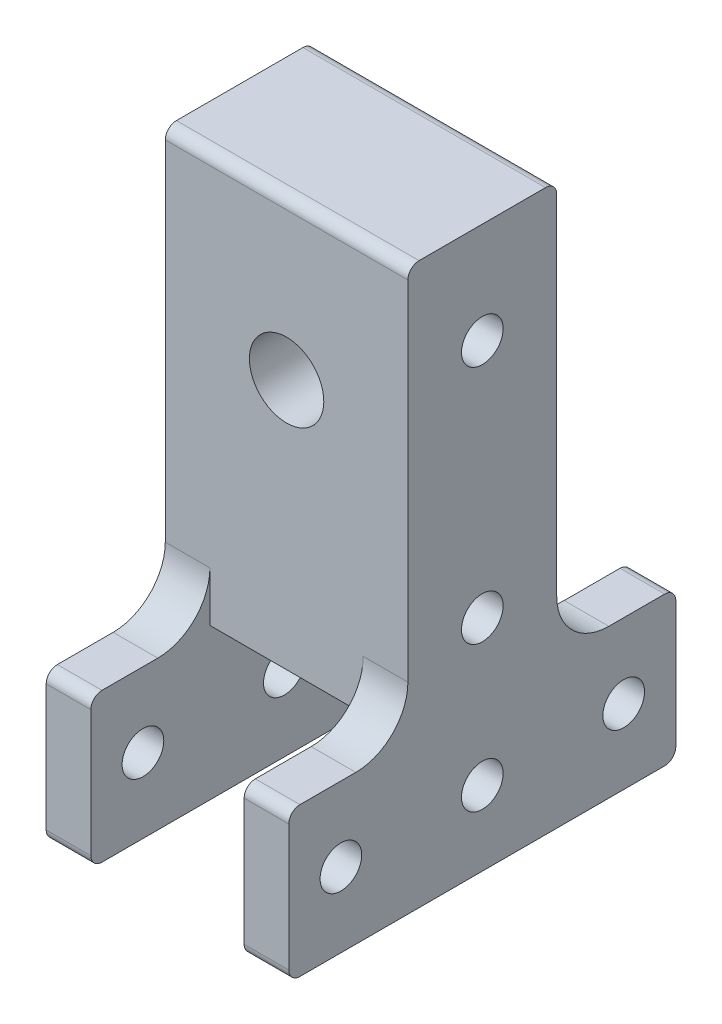
SolidWorks part; units mm, degrees
ref_plane "Front plane" through (0, 0, 0) normal (0, 0, 1) x (1, 0, 0)
ref_plane "Top plane" through (0, 0, 0) normal (0, 1, 0) x (1, 0, 0)
ref_plane "Right plane" through (0, 0, 0) normal (1, 0, 0) x (0, 0, -1)
ref_axis "Axis X" through (0, 0, 0) along (1, 0, 0)
ref_axis "Axis Y" through (0, 0, 0) along (0, 1, 0)
ref_axis "Axis Z" through (0, 0, 0) along (0, 0, 1)
sketch "Sketch1" plane through (0, 0, 0) normal (1, 0, 0) x (0, 0, -1)
  line L1 (10, 65.3) -> (-10, 65.3)
  line L2 (10, 65.3) -> (10, 10.3)
  line L3 (10, 10.3) -> (-10, 10.3)
  line L4 (-10, 65.3) -> (-10, 10.3)
  line L5 (10, 65.3) -> (-10, 10.3) construction
  line L6 (10, 10.3) -> (-10, 65.3) construction
  point P0 (0, 37.8)
  dimension "D1" = 10.3
  dimension "D2" = 20
  dimension "D3" = 55
extrude "Extrude1" add sketch "Sketch1" along normal blind 10.3 and the other way blind 10.3
sketch "Sketch2" plane through (10.3, 0, 0) normal (1, 0, 0) x (0, 0, -1)
  line L0 (10, 10.3) -> (10, 65.3) construction
  line L1 (26, 10) -> (17, 10)
  line L2 (26, 10) -> (26, -10)
  line L3 (26, -10) -> (-26, -10)
  line L4 (-26, 10) -> (-26, -10)
  line L5 (26, 10) -> (-26, -10) construction
  line L6 (26, -10) -> (-26, 10) construction
  line L7 (-10, 65.3) -> (10, 65.3)
  line L8 (-10, 65.3) -> (-10, 17)
  line L9 (-10, 10) -> (10, 10) construction
  line L10 (10, 65.3) -> (10, 17)
  line L11 (-17, 10) -> (-26, 10)
  line L12 (10, 10) -> (-10, 10) construction
  arc A0 (17, 10) -> (10, 17) centre (17, 17) cw
  arc A1 (-17, 10) -> (-10, 17) centre (-17, 17) ccw
  point P0 (0, 0)
  dimension "D3" = 7
  dimension "D1" = 20
  dimension "D2" = 52
extrude "Extrude2" add sketch "Sketch2" along normal blind 6
mirror "Mirror2" about plane through (0, 0, 0) normal (1, 0, 0) of "Extrude2"
sketch "Sketch4" plane through (16.3, 0, 0) normal (1, 0, 0) x (0, 0, -1)
  line L0 (0, 2.8) -> (0, -2.8) construction
  circle A0 centre (0, 0) radius 2.8
  circle A1 centre (19, 0) radius 2.8
  circle A2 centre (-19, 0) radius 2.8
  circle A3 centre (0, 19.5) radius 2.8
  circle A4 centre (0, 51.75) radius 2.8
  dimension "D1" = 5.6
  dimension "D2" = 5.6
  dimension "D4" = 5.6
  dimension "D5" = 5.6
  dimension "D3" = 19
  dimension "D6" = 32.25
  dimension "D7" = 19.5
extrude "Extrude3" cut sketch "Sketch4" against normal through all
sketch "Sketch5" plane through (0, 0, 10) normal (0, 0, 1) x (1, 0, 0)
  line L0 (-16.3, 19.5) -> (16.3, 19.5) construction
  line L1 (-16.3, 65.3) -> (-16.3, 17) construction
  line L2 (16.3, 65.3) -> (16.3, 17) construction
  line L3 (-16.3, 22.3) -> (16.3, 22.3) construction
  line L4 (-16.3, 16.7) -> (16.3, 16.7) construction
  line L5 (-16.3, 54.55) -> (16.3, 54.55) construction
  line L6 (-16.3, 51.75) -> (16.3, 51.75) construction
  line L7 (-16.3, 48.95) -> (16.3, 48.95) construction
  line L8 (-5, 44) -> (5, 44) construction
  line L9 (-10.3, 10) -> (10.3, 10) construction
  line L10 (-10.3, 10) -> (-10.3, -10) construction
  line L11 (10.3, 10) -> (10.3, -10) construction
  circle A0 centre (0, 44) radius 5
  dimension "D1" = 5.6
  dimension "D2" = 5.6
  dimension "D5" = 10
  dimension "D3" = 19.5
  dimension "D4" = 32.25
  dimension "D7" = 10
  dimension "D8" = 34
extrude "Extrude4" cut sketch "Sketch5" against normal through all
fillet "Fillet2" radius 1.5 10 edges at (13.3, -10, 26) (13.3, 10, 26) (-13.3, 10, 26) (-13.3, -10, 26) (-13.3, -10, -26) (13.3, -10, -26) (13.3, 10, -26) (-13.3, 10, -26) (0, 65.3, 10) (0, 65.3, -10)
equation "\"bearing_d1\"= 5"
equation "\"bearing_d2\"= 10"
equation "\"print_offset\"= 0.6"
equation "\"bearing_h\"=15"
equation "\"prof_width\"= 20'Aluminium profile parameters"
equation "\"prof_groove\"= 6"
equation "\"prof_length\"= 410"
equation "\"prof_screw_diameter\"= 4"
equation "\"screw2_diameter\"= 2"
equation "\"screw2_diameter_ext\"= 4"
equation "\"screw2_heigh_head\"= 2"
equation "\"nut2_diameter\"= 4"
equation "\"nut2_heigh\"= 2"
equation "\"screw_offset_ext\"= 2"
equation "\"angle_heigh\"= 50'Angle mount parameters"
equation "\"angle_thikness\"= 3"
equation "\"angle_width\"= 30"
equation "\"mount_thikness\"= 15'Other mounts parameters"
equation "\"mount_screw\"= 4"
equation "\"mount_screw_distance\"= 40"
equation "\"bearings_distance\"= 22"
equation "\"tape_distance\"= 7.35"
equation "\"bearing_grove_d1\"= 4"
equation "\"bearing_grove_d2\"= 13"
equation "\"bearing_grove_h\"= 4"
equation "\"bearing_groove_r\"= 1"
equation "\"D1@Sketch1\"=(\"prof_width\"+\"print_offset\")/2"
equation "\"D3@Sketch1\"=55.00mm"
equation "\"D1@Extrude1\"=(\"prof_width\"+\"print_offset\")/2"
equation "\"D2@Extrude1\"=(\"prof_width\"+\"print_offset\")/2"
equation "\"D1@Sketch2\"=\"prof_width\""
equation "\"D1@Sketch4\"=\"print_offset\"+5"
equation "\"D2@Sketch4\"=\"D1@Sketch4\""
equation "\"D4@Sketch4\"=\"D1@Sketch4\""
equation "\"D5@Sketch4\"=\"D1@Sketch4\""
equation "\"D2@Sketch5\"=\"D1@Sketch5\""
equation "\"D1@Sketch5\"=\"print_offset\"+5.00mm"
equation "\"D7@Sketch5\"=\"prof_width\"/2"
